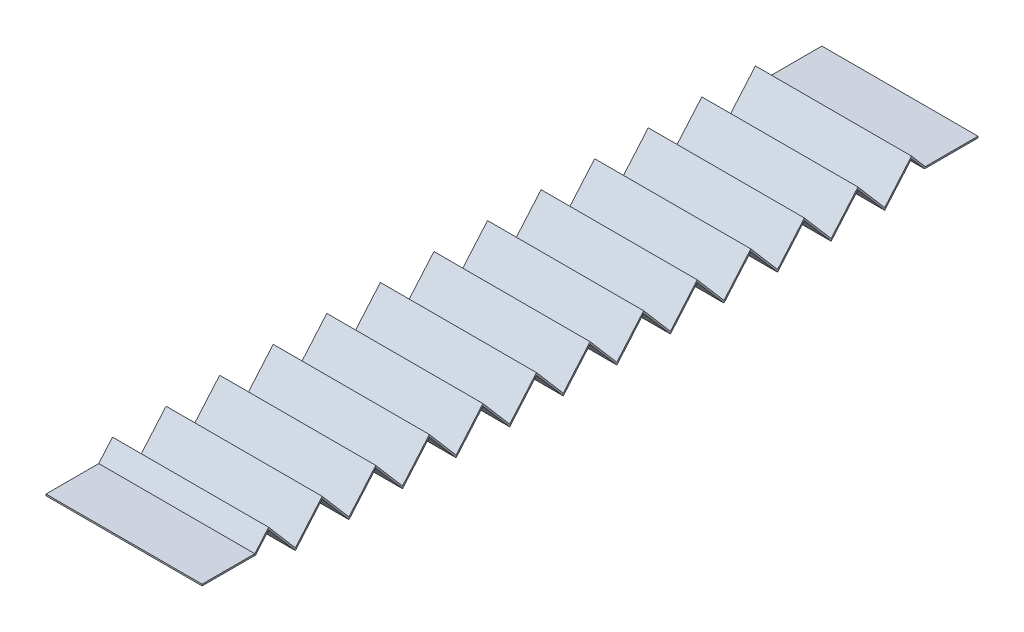
SolidWorks part; units mm, degrees
ref_plane "Front Plane" through (0, 0, 0) normal (0, 0, 1) x (1, 0, 0)
ref_plane "Top Plane" through (0, 0, 0) normal (0, 1, 0) x (1, 0, 0)
ref_plane "Right Plane" through (0, 0, 0) normal (1, 0, 0) x (0, 0, -1)
sketch "Sketch2" plane through (0, 0, 0) normal (0, 0, 1) x (1, 0, 0)
  line L1 (-27.5, 10) -> (27.5, 10)
  line L2 (-27.5, 10) -> (-27.5, 0)
  line L3 (-27.5, 0) -> (27.5, 0)
  line L4 (27.5, 10) -> (27.5, 0)
  point P4 (0, 0)
  dimension "D1" = 10
  dimension "D2" = 55
sketch "Sketch3" plane through (0, 0, 0) normal (1, 0, 0) x (0, 0, -1)
  line L0 (0, 10) -> (248.4692, 10) construction
  line L1 (0, 0) -> (248.4692, 0) construction
  line L3 (17, 5) -> (21.2894, 10)
  line L4 (21.2894, 10) -> (29.8682, 0)
  line L5 (29.8682, 0) -> (38.4469, 10)
  line L6 (38.4469, 10) -> (47.0257, 0)
  line L7 (47.0257, 0) -> (55.6045, 10)
  line L8 (55.6045, 10) -> (64.1832, 0)
  line L9 (64.1832, 0) -> (72.762, 10)
  line L10 (72.762, 10) -> (81.3408, 0)
  line L11 (81.3408, 0) -> (89.9195, 10)
  line L12 (89.9195, 10) -> (98.4983, 0)
  line L13 (98.4983, 0) -> (107.0771, 10)
  line L14 (107.0771, 10) -> (115.6558, 0)
  line L15 (115.6558, 0) -> (124.2346, 10)
  line L16 (124.2346, 10) -> (132.8134, 0)
  line L17 (132.8134, 0) -> (141.3921, 10)
  line L18 (141.3921, 10) -> (149.9709, 0)
  line L19 (0, 10) -> (0, 0) construction
  line L20 (149.9709, 0) -> (158.5497, 10)
  line L21 (158.5497, 10) -> (167.1284, 0)
  line L22 (167.1284, 0) -> (175.7072, 10)
  line L23 (175.7072, 10) -> (184.286, 0)
  line L24 (184.286, 0) -> (192.8647, 10)
  line L25 (192.8647, 10) -> (201.4435, 0)
  line L26 (201.4435, 0) -> (210.0223, 10)
  line L27 (210.0223, 10) -> (218.601, 0)
  line L28 (218.601, 0) -> (227.1798, 10)
  line L29 (227.1798, 10) -> (231.4692, 5)
  line L30 (248.4692, 10) -> (248.4692, 0) construction
  line L31 (17, 5) -> (0, 5)
  line L32 (231.4692, 5) -> (248.4692, 5)
  line L34 (248.4692, 4.75) -> (248.4692, 22.75) construction
  dimension "D2" = 17
  dimension "D1" = 10
  dimension "D3" = 17
extrude "Extrude-Thin1" add sketch "Sketch3" against normal mid plane 50 thin thin type mid plane wall 0.5
